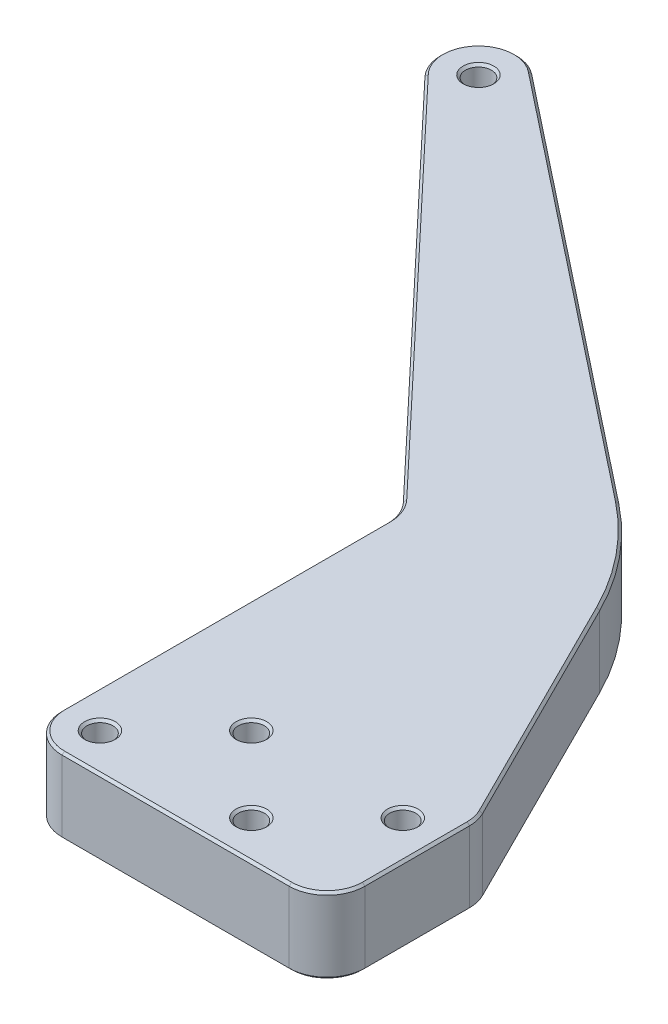
SolidWorks part; units mm, degrees
ref_plane "Front Plane" through (0, 0, 0) normal (0, 0, 1) x (1, 0, 0)
ref_plane "Top Plane" through (0, 0, 0) normal (0, 1, 0) x (1, 0, 0)
ref_plane "Right Plane" through (0, 0, 0) normal (1, 0, 0) x (0, 0, -1)
sketch "Sketch1" plane through (0, 0, 0) normal (0, 1, 0) x (1, 0, 0)
  line L0 (-6.35, 0) -> (-6.35, 54.6279)
  line L1 (-8.0805, 58.9848) -> (-68.1195, 122.6431)
  line L2 (-59.5626, 131.9819) -> (10.1729, 76.8661)
  line L3 (24.1102, 59.7296) -> (43.7796, 20.3908)
  line L4 (44.45, 17.551) -> (44.45, 0)
  line L5 (38.1, -6.35) -> (0, -6.35)
  circle A0 centre (0, 0) radius 2.1828
  circle A1 centre (12.7, 12.7) radius 2.1828
  circle A2 centre (25.4, 0) radius 2.1828
  circle A3 centre (38.1, 12.7) radius 2.1828
  circle A4 centre (-63.5, 127) radius 2.1828
  arc A5 (-59.5626, 131.9819) -> (-68.1195, 122.6431) centre (-63.5, 127) ccw
  arc A6 (-6.35, 54.6279) -> (-8.0805, 58.9848) centre (-12.7, 54.6279) ccw
  arc A7 (43.7796, 20.3908) -> (44.45, 17.551) centre (38.1, 17.551) cw
  arc A8 (44.45, 0) -> (38.1, -6.35) centre (38.1, 0) cw
  arc A9 (-6.35, 0) -> (0, -6.35) centre (0, 0) ccw
  arc A10 (10.1729, 76.8661) -> (24.1102, 59.7296) centre (-21.3267, 37.0111) cw
  point P20 (-6.35, 57.15)
  point P23 (44.45, 19.05)
  point P28 (-6.35, -6.35)
  point P31 (19.05, 69.85)
  dimension "D5" = 4.3656
  dimension "D6" = 4.3656
  dimension "D7" = 4.3656
  dimension "D8" = 4.3656
  dimension "D11" = 4.3656
  dimension "D12" = 12.7
  dimension "D20" = 6.35
  dimension "D21" = 50.8
  dimension "D1" = 12.7
  dimension "D2" = 12.7
  dimension "D3" = 12.7
  dimension "D4" = 12.7
  dimension "D9" = 127
  dimension "D10" = 63.5
  dimension "D13" = 6.35
  dimension "D14" = 6.35
  dimension "D15" = 6.35
  dimension "D16" = 6.35
  dimension "D17" = 63.5
  dimension "D18" = 50.8
  dimension "D19" = 25.4
extrude "Boss-Extrude1" add sketch "Sketch1" along normal blind 12.7
chamfer "Chamfer1" distance 0.3969 angle 45 34 edges at (-63.5, 0, -124.8172) (38.1, 0, -10.5172) (25.4, 0, 2.1828) (12.7, 0, -10.5172) (0, 0, 2.1828) (-6.35, 0, -27.314) (-4.4901, 0, 4.4901) (19.05, 0, 6.35) (42.5901, 0, 4.4901) (44.45, 0, -8.7755) (44.2801, 0, -19.0099) (33.9449, 0, -40.0602) (18.0842, 0, -69.0645) (-24.6948, 0, -104.424) (-68.1818, 0, -131.2899) (-38.1, 0, -90.814) (-6.7985, 0, -56.9719) (-63.5, 12.7, -124.8172) (25.4, 12.7, 2.1828) (0, 12.7, 2.1828) (-38.1, 12.7, -90.814) (-68.1818, 12.7, -131.2899) (-24.6948, 12.7, -104.424) (18.0842, 12.7, -69.0645) (33.9449, 12.7, -40.0602) (44.2801, 12.7, -19.0099) (44.45, 12.7, -8.7755) (42.5901, 12.7, 4.4901) (19.05, 12.7, 6.35) (-4.4901, 12.7, 4.4901) (-6.35, 12.7, -27.314) (-6.7985, 12.7, -56.9719) (12.7, 12.7, -10.5172) (38.1, 12.7, -10.5172)
